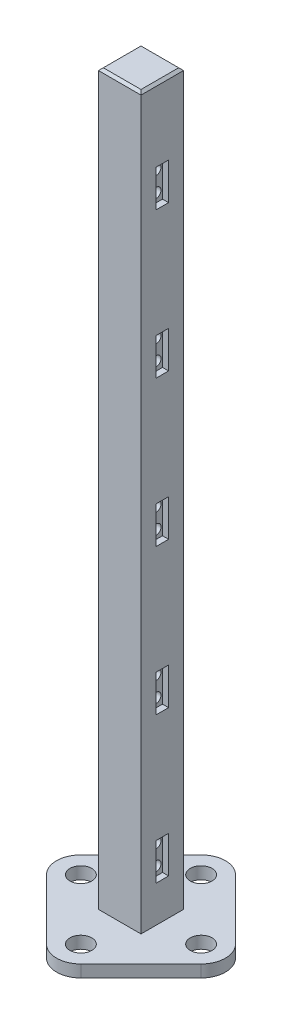
SolidWorks part; units mm, degrees
ref_plane "Front" through (0, 0, 0) normal (0, 0, 1) x (1, 0, 0)
ref_plane "Top" through (0, 0, 0) normal (0, 1, 0) x (1, 0, 0)
ref_plane "Right" through (0, 0, 0) normal (1, 0, 0) x (0, 0, -1)
ref_axis "Axis1" through (0, 55, 0) along (0, -1, 0)
ref_axis "Axis2" through (88.99, 0, 0) along (-1, 0, 0)
ref_axis "Axis3" through (0, 0, 55) along (0, 0, -1)
sketch "Sketch1" plane through (0, 0, 0) normal (0, 1, 0) x (1, 0, 0)
  line L0 (-24.75, 0) -> (0, 24.75) construction
  line L9 (-24.75, 0) -> (0, -24.75) construction
  line L11 (0, 24.75) -> (24.75, 0) construction
  line L12 (0, -24.75) -> (24.75, 0) construction
  line L13 (-24.75, 0) -> (24.75, 0) construction
  line L14 (0, 24.75) -> (0, -24.75) construction
  line L15 (-31.8211, 7.0711) -> (-7.0711, 31.8211)
  line L16 (7.0711, 31.8211) -> (31.8211, 7.0711)
  line L17 (7.0711, -31.8211) -> (31.8211, -7.0711)
  line L18 (-31.8211, -7.0711) -> (-7.0711, -31.8211)
  line L19 (0, -38.8921) -> (38.8921, 0) construction
  line L20 (-38.8921, 0) -> (0, -38.8921) construction
  line L21 (0, 38.8921) -> (38.8921, 0) construction
  line L22 (-38.8921, 0) -> (0, 38.8921) construction
  arc A4 (7.0711, -31.8211) -> (-7.0711, -31.8211) centre (0, -24.75) cw
  arc A5 (31.8211, 7.0711) -> (31.8211, -7.0711) centre (24.75, 0) cw
  arc A6 (-7.0711, 31.8211) -> (7.0711, 31.8211) centre (0, 24.75) cw
  arc A7 (-31.8211, 7.0711) -> (-31.8211, -7.0711) centre (-24.75, 0) ccw
  circle A8 centre (0, 24.75) radius 4.5
  circle A9 centre (24.75, 0) radius 4.5
  circle A10 centre (0, -24.75) radius 4.5
  circle A11 centre (-24.75, 0) radius 4.5
  point P1 (0, 0)
  dimension "D3" = 10
  dimension "D4" = 9
  dimension "D1" = 49.5
  dimension "D2" = 10
extrude "Boss-Extrude1" add sketch "Sketch1" along normal mid plane 5
sketch "Sketch2" plane through (0, 2.5, 0) normal (0, 1, 0) x (1, 0, 0)
  line L0 (-8.75, 8.75) -> (8.75, -8.75) construction
  line L1 (-8.75, 8.75) -> (8.75, 8.75)
  line L2 (-8.75, 8.75) -> (-8.75, -8.75)
  line L3 (-8.75, -8.75) -> (8.75, -8.75)
  line L4 (8.75, 8.75) -> (8.75, -8.75)
  line L5 (-7.0711, 31.8211) -> (-31.8211, 7.0711) construction
  dimension "D1" = 17.5
extrude "Boss-Extrude2" add sketch "Sketch2" along normal blind 300
sketch "Sketch3" plane through (8.75, 0, 0) normal (1, 0, 0) x (0, 0, -1)
  line L0 (7.0711, 2.5) -> (31.8211, 2.5) construction
  line L1 (-2.6, 17.5) -> (2.6, 17.5)
  line L2 (-2.6, 17.5) -> (-2.6, 32.7)
  line L3 (-2.6, 32.7) -> (2.6, 32.7)
  line L4 (2.6, 17.5) -> (2.6, 32.7)
  point P4 (0, 17.5)
  dimension "D1" = 5.2
  dimension "D2" = 15.2
  dimension "D3" = 15
extrude "Cut-Extrude1" cut sketch "Sketch3" against normal blind 2.5
hole_wizard "Ø4.0mm Dowel Hole1" positions "Sketch5" profile "Sketch6" hole size "Ø4.0" standard "DIN" end condition through all
sketch "Sketch5" plane through (6.25, 0, 0) normal (1, 0, 0) x (0, 0, -1)
  line L0 (0, 32.7) -> (0, 29.2) construction
  line L1 (2.6, 32.7) -> (-2.6, 32.7) construction
  line L2 (0, 29.2) -> (0, 21) construction
  line L3 (0, 21) -> (0, 17.5) construction
  line L4 (-2.6, 17.5) -> (2.6, 17.5) construction
  point P0 (0, 21)
  point P2 (0, 29.2)
  dimension "D1" = 3.5
sketch "Sketch6" plane through (6.25, 21, 0) normal (0, 1, 0) x (0, 0, -1)
  line L0 (0, 0) -> (0, 41)
  line L1 (0, 41) -> (2, 41)
  line L2 (2, 41) -> (2, 0)
  line L5 (2, 0) -> (0, 0)
  line L11 (0, -6.35) -> (0, 107.95) construction
  dimension "Thru Hole Dia." = 4
  dimension "Thru Hole Depth" = 41
pattern_linear "LPattern1" count 5 spacing 60 along (0, 1, 0) of "Ø4.0mm Dowel Hole1", "Cut-Extrude1"
chamfer "Chamfer1" distance 1 angle 45 4 edges at (0, 302.5, -8.75) (8.75, 302.5, 0) (0, 302.5, 8.75) (-8.75, 302.5, 0)
